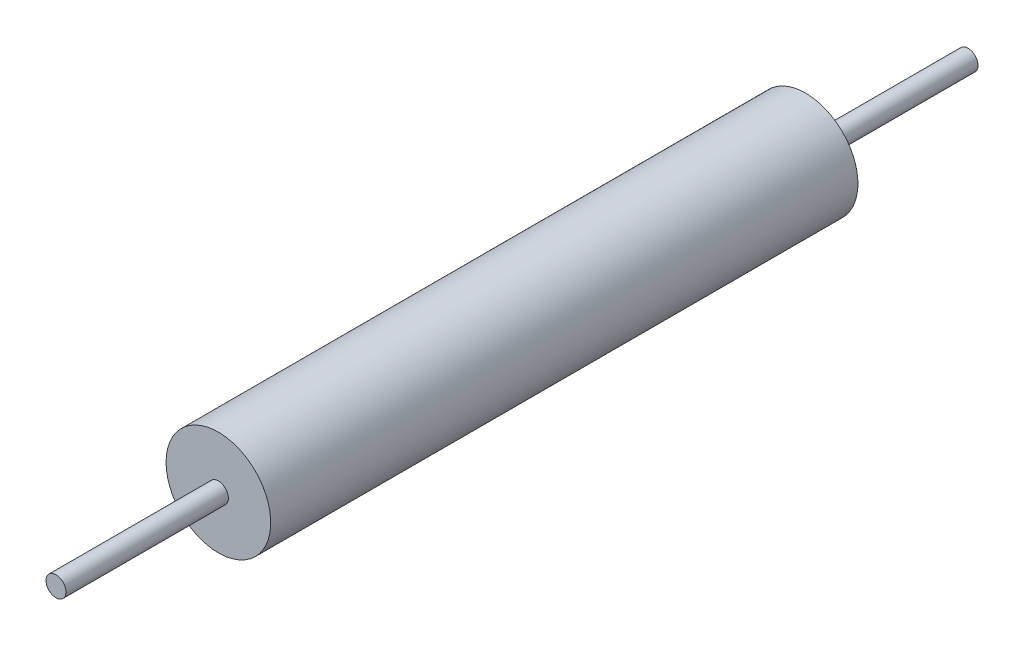
SolidWorks part; units mm, degrees
material "1060 Alloy"
ref_plane "Front Plane" through (0, 0, 0) normal (0, 0, 1) x (1, 0, 0)
ref_plane "Top Plane" through (0, 0, 0) normal (0, 1, 0) x (1, 0, 0)
ref_plane "Right Plane" through (0, 0, 0) normal (1, 0, 0) x (0, 0, -1)
sketch "Sketch1" plane through (0, 0, 0) normal (0, 0, 1) x (1, 0, 0)
  circle A0 centre (0, 0) radius 4
  circle A1 centre (0, 0) radius 3.95
  circle A2 centre (0, 0) radius 20.94
  dimension "D1" = 8
  dimension "D2" = 7.9
  dimension "D3" = 41.88
extrude "Boss-Extrude1" add sketch "Sketch1" along normal blind 235 contours A2 A0 | A0 A1 | A1 region at (-3.9887, 0, 0) region at (0, 0, 0) region at (-20.3477, 0, 0)
extrude "Boss-Extrude2" add sketch "Sketch1<3>" against normal blind 65 contours A0
sketch "Sketch1<3>" plane through (0, 0, 0) normal (0, 0, 1) x (1, 0, 0) same geometry as "Sketch1"
extrude "Boss-Extrude4" add sketch "Sketch1<5>" along normal blind 65 from surface contours A1 | A0 A1 region at (-3.9887, 0, 0) region at (0, 0, 0) starting at face at (20.94, 0, 235)
sketch "Sketch1<5>" plane through (0, 0, 0) normal (0, 0, 1) x (1, 0, 0) same geometry as "Sketch1"
